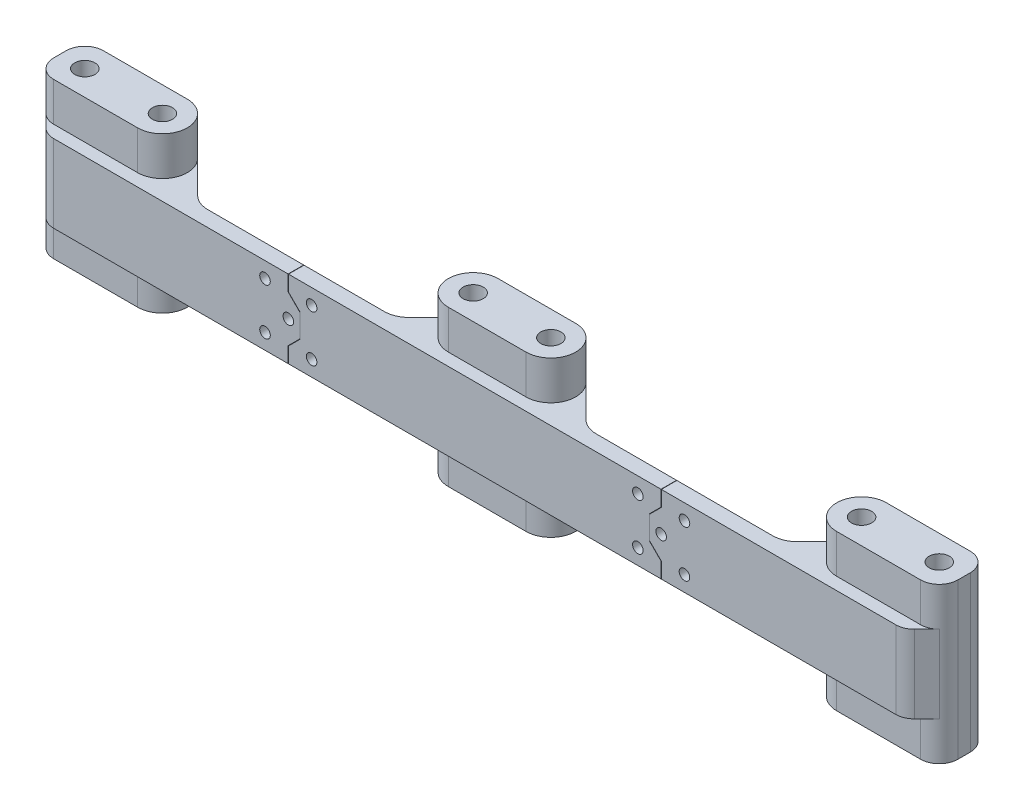
SolidWorks part; units mm, degrees
material "ABS"
ref_plane "Front Plane" through (0, 0, 0) normal (0, 0, 1) x (1, 0, 0)
ref_plane "Top Plane" through (0, 0, 0) normal (0, 1, 0) x (1, 0, 0)
ref_plane "Right Plane" through (0, 0, 0) normal (1, 0, 0) x (0, 0, -1)
ref_axis "X" through (-152.775, 0, 0) along (1, 0, 0)
ref_axis "Y" through (0, 27.5, 0) along (0, -1, 0)
ref_axis "Z" through (0, 0, -21) along (0, 0, 1)
sketch "Sketch1" plane through (0, 0, 0) normal (0, 1, 0) x (1, 0, 0)
  line L0 (0, 0) -> (-135.5, 0)
  line L2 (-139.5, 20) -> (-112.5, 20)
  line L3 (-106.8431, 17.6569) -> (-96.5294, 7.3431)
  line L4 (-90.8726, 5) -> (-34.1274, 5)
  line L5 (0, 12) -> (0, 0)
  line L6 (0, 20) -> (-12.5, 20)
  line L7 (-18.1569, 17.6569) -> (-28.4706, 7.3431)
  line L8 (-137.5, 12) -> (-112.5, 12) construction
  line L9 (-112.5, 12) -> (-12.5, 12) construction
  line L10 (0, 20) -> (0, 12)
  line L11 (-12.5, 12) -> (0, 12) construction
  line L12 (-145.5, 14) -> (-145.5, 10)
  line L13 (-143.7426, 5.7574) -> (-139.7426, 1.7574)
  line L14 (-137.5, 12) -> (-145.5, 12) construction
  line L15 (-12.5, 4) -> (0, 4)
  line L16 (-112.5, 4) -> (-139.5, 4)
  arc A1 (-112.5, 20) -> (-106.8431, 17.6569) centre (-112.5, 12) cw
  arc A2 (-96.5294, 7.3431) -> (-90.8726, 5) centre (-90.8726, 13) ccw
  arc A3 (-12.5, 20) -> (-18.1569, 17.6569) centre (-12.5, 12) ccw
  arc A4 (-28.4706, 7.3431) -> (-34.1274, 5) centre (-34.1274, 13) cw
  circle A5 centre (-12.5, 12) radius 3.25
  circle A6 centre (-112.5, 12) radius 3.25
  circle A7 centre (-137.5, 12) radius 3.25
  arc A8 (-135.5, 0) -> (-139.7426, 1.7574) centre (-135.5, 6) cw
  arc A9 (-145.5, 10) -> (-143.7426, 5.7574) centre (-139.5, 10) ccw
  arc A10 (-145.5, 14) -> (-139.5, 20) centre (-139.5, 14) cw
  arc A11 (-106.8431, 17.6569) -> (-104.5, 12) centre (-112.5, 12) cw
  arc A12 (-104.5, 12) -> (-112.5, 4) centre (-112.5, 12) cw
  arc A13 (-139.5, 4) -> (-143.7426, 5.7574) centre (-139.5, 10) cw
  arc A14 (-18.1569, 17.6569) -> (-12.5, 4) centre (-12.5, 12) ccw
  dimension "D1" = 6.5
  dimension "D2" = 5
  dimension "D4" = 4
  dimension "D6" = 45
  dimension "D12" = 8
  dimension "D11" = 8
  dimension "D3" = 12.5
  dimension "D5" = 45
  dimension "D7" = 25
  dimension "D8" = 100
  dimension "D9" = 45
  dimension "D10" = 12
extrude "Boss-Extrude1" add sketch "Sketch1" against normal mid plane 25 contours A14 L7 A4 L4 A2 L3 A11 A12 L16 A13 L13 A8 L0 L5 L15 | A13 L16 A12 A11 A1 L2 A10 L12 A9 A7 A6 | A3 A14 L15 L5 L10 L6 A5 region at (-67.8635, 0, -3.3443) region at (-9.1012, 0, -12) region at (-125.3987, 0, -12)
sketch "Sketch2" plane through (0, 0, 0) normal (0, 0, 1) x (1, 0, 0)
  line L0 (0, 0) -> (-60, 0) construction
  line L2 (-52.5, 7.5) -> (-67.5, 7.5) construction
  line L3 (-52.5, 7.5) -> (-52.5, -7.5) construction
  line L4 (-52.5, -7.5) -> (-67.5, -7.5) construction
  line L5 (-67.5, 7.5) -> (-67.5, -7.5) construction
  line L6 (-52.5, 7.5) -> (-67.5, -7.5) construction
  line L7 (-52.5, -7.5) -> (-67.5, 7.5) construction
  line L8 (-60, 7.5) -> (-56.25, 3.75)
  line L9 (-56.25, 3.75) -> (-56.25, -3.75)
  line L10 (-56.25, -3.75) -> (-60, -7.5)
  line L11 (-60, -7.5) -> (-60, -12.5)
  line L14 (-60, 7.5) -> (-60, 12.5)
  line L18 (0, 12.5) -> (0, -12.5) construction
  line L25 (0, -12.5) -> (-135.5, -12.5) construction
  line L26 (0, 12.5) -> (-135.5, 12.5) construction
  point P42 (0, 0)
  point P43 (0, 0)
  point P46 (0, 0)
  point P49 (0, -12.5)
  point P50 (0, -3.1838)
  point P51 (0, -25)
  point P53 (0, 0)
  point P54 (-60, 2.5)
  point P55 (-60, -25)
  point P58 (-60, 0)
  point P61 (0, 0)
  dimension "D1" = 15
  dimension "D2" = 60
extrude "Boss-Extrude2" add sketch "Sketch1<3>" along normal mid plane 50 contours A13 L16 A12 A11 A1 L2 A10 L12 A9 A7 A6 | A3 A14 L15 L5 L10 L6 A5 region at (-9.1012, 0, -12) region at (-125.3987, 0, -12)
sketch "Sketch1<3>" plane through (0, 0, 0) normal (0, 1, 0) x (1, 0, 0) same geometry as "Sketch1"
sketch "Sketch6" plane through (0, 0, -5) normal (0, 0, -1) x (-1, 0, 0)
  line L0 (52.5, -7.5) -> (67.5, 7.5) construction
  point P0 (52.5, 7.5)
  point P3 (67.5, 7.5)
  point P6 (60, 0)
  point P10 (67.5, -7.5)
  point P13 (52.5, -7.5)
hole_wizard "M3 Clearance Hole1" positions "Sketch6" profile "Sketch5" hole size "M3" standard "ANSI Metric"
sketch "Sketch5" plane through (-52.5, 7.5, -5) normal (1, 0, 0) x (0, 1, 0)
  line L0 (0, 0) -> (0, 10)
  line L1 (0, 10) -> (1.7, 8.9785)
  line L2 (1.7, 8.9785) -> (1.7, 0)
  line L5 (1.7, 0) -> (0, 0)
  line L10 (0, 10) -> (-1.7, 8.9785) construction
  line L11 (0, -6.35) -> (0, 107.95) construction
  dimension "Hole Dia." = 3.4
  dimension "Hole Depth" = 10
  dimension "Drill Angle" = 118
extrude "Cut-Extrude-Thin1" cut sketch "Sketch2" against normal blind 10 and the other way through all thin thin type mid plane wall 0.1
mirror "Mirror1" about plane through (0, 0, 0) normal (1, 0, 0) of bodies 105 104 101
combine bodies "Combine1" operation type add bodies to combine 105 106
